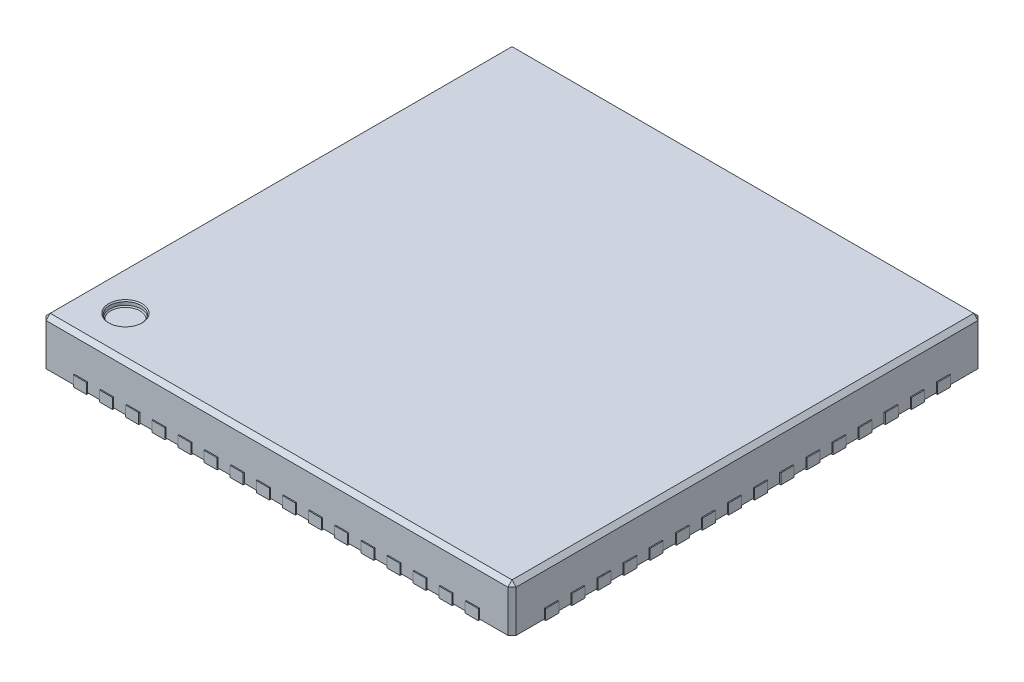
SolidWorks part; units mm, degrees
ref_plane "Front Plane" through (0, 0, 0) normal (0, 0, 1) x (1, 0, 0)
ref_plane "Top Plane" through (0, 0, 0) normal (0, 1, 0) x (1, 0, 0)
ref_plane "Right Plane" through (0, 0, 0) normal (1, 0, 0) x (0, 0, -1)
sketch "Sketch1" plane through (0, 0, 0) normal (1, 0, 0) x (0, 0, -1)
  line L0 (0, 0) -> (0, 3.0677) construction
sketch3d "3DSketch1"
  line L1 (-4.5, 0.02, 4.5) -> (4.5, 0.02, 4.5)
  line L2 (-4.5, 0.02, 4.5) -> (-4.5, 0.02, -4.5)
  line L3 (-4.5, 0.02, -4.5) -> (4.5, 0.02, -4.5)
  line L4 (4.5, 0.02, 4.5) -> (4.5, 0.02, -4.5)
  line L5 (-4.5, 0.02, 4.5) -> (4.5, 0.02, -4.5) construction
  line L6 (-4.5, 0.02, -4.5) -> (4.5, 0.02, 4.5) construction
  point P0 (0, 0.02, 0)
  dimension "D1" = 0.02
  dimension "D2" = 9
  dimension "D3" = 9
extrude "Boss-Extrude1" add sketch "3DSketch1" along direction (0, 1, 0) on the side of the normal blind 0.88 separate body
chamfer "Chamfer1" distance 0.08 angle 45 8 edges
sketch "Sketch2" plane through (0, 0.9, 0) normal (0, 1, 0) x (1, 0, 0)
  line L0 (-4.42, -4.5) -> (-4.42, -3.7) construction
  line L1 (-4.42, 4.42) -> (-4.42, -4.42) construction
  line L2 (-4.5, -4.42) -> (-3.7, -4.42) construction
  line L3 (-4.42, -4.42) -> (4.42, -4.42) construction
  line L4 (-3.7, -4.42) -> (-3.7, -3.7) construction
  circle A0 centre (-3.7, -3.7) radius 0.3
  dimension "D3" = 0.6
  dimension "D1" = 0.8
  dimension "D2" = 0.8
extrude "Cut-Extrude1" cut sketch "Sketch2" against normal blind 0.1
chamfer "Chamfer2" distance 0.02 angle 45 2 edges at (-3.7, 0.9, 4) (-3.7, 0.8, 4)
sketch "Sketch3" plane through (0, 0, 0) normal (0, 1, 0) x (1, 0, 0)
  line L0 (0, 0) -> (0, 4.52) construction
  line L1 (0.25, 4.52) -> (0.25, 4.6401) construction
  line L2 (0, 4.52) -> (0, 4.6401) construction
  line L3 (0.25, 4.6401) -> (0, 4.6401) construction
  line L4 (0, 4.52) -> (0.4269, 4.52) construction
  line L5 (0.4269, 4.52) -> (0.4269, 0) construction
  line B0 (0.25, 4.52) -> (0.375, 4.52) construction
  line B1 (0.125, 4.225) -> (0.375, 4.225) construction
  line B2 (0.375, 4.52) -> (0.125, 4.52)
  line B3 (0.375, 4.52) -> (0.375, 4.225)
  line B4 (0.25, 4.1) -> (0.5, 4.1) construction
  line B5 (0.125, 4.52) -> (0.125, 4.225)
  line B6 (0.375, 4.52) -> (0.5, 4.52) construction
  line B7 (0.5, 4.52) -> (0.5, 4.1) construction
  arc B8 (0.375, 4.225) -> (0.125, 4.225) centre (0.25, 4.225) cw
  dimension "D1" = 0.25
  dimension "D2" = 4.52
sketch_block_instance "Block4-1"
sketch_block "Block4" parameters "D1"=0.125, "D2"=0.25, "D3"=0.45, "D4"=0.42
extrude "Boss-Extrude2" add sketch "Sketch3" along normal blind 0.2
pattern_linear "LPattern1" count 8 spacing 0.5 along (1, 0, 0) of bodies 102
pattern_linear "LPattern2" count 9 spacing 0.5 along (-1, 0, 0) of bodies 102
pattern_circular "CirPattern2" count 4 over 360 about axis through (0, 0, 0) along (0, 1, 0) of bodies 158 157 156 155 151 150 149 102 167 168 169 238 239 240 241 242
sketch "Sketch4" plane through (0, 0, 0) normal (0, 1, 0) x (1, 0, 0)
  line L8 (-3.178, -3.55) -> (3.45, -3.55)
  line L9 (-3.45, 3.55) -> (3.45, 3.55)
  line L10 (-3.55, -3.178) -> (-3.55, 3.45)
  line L12 (3.55, 3.45) -> (3.55, -3.45)
  line L13 (-3.55, 3.55) -> (3.55, -3.55) construction
  line L14 (-3.55, -3.55) -> (3.55, 3.55) construction
  arc A6 (3.55, 3.45) -> (3.45, 3.55) centre (3.45, 3.45) ccw
  arc A7 (-3.45, 3.55) -> (-3.55, 3.45) centre (-3.45, 3.45) ccw
  arc A8 (3.45, -3.55) -> (3.55, -3.45) centre (3.45, -3.45) ccw
  arc A9 (-3.198, -3.5311) -> (-3.5311, -3.198) centre (-3.55, -3.55) ccw
  arc A10 (-3.198, -3.5311) -> (-3.178, -3.55) centre (-3.178, -3.53) ccw
  arc A11 (-3.5311, -3.198) -> (-3.55, -3.178) centre (-3.53, -3.178) cw
  dimension "D7" = 0.1
  dimension "D8" = 0.1
  dimension "D9" = 0.1
  dimension "D10" = 0.02
  dimension "D5" = 7.1
  dimension "D6" = 7.1
extrude "Boss-Extrude3" add sketch "Sketch4" along normal blind 0.2 separate body
